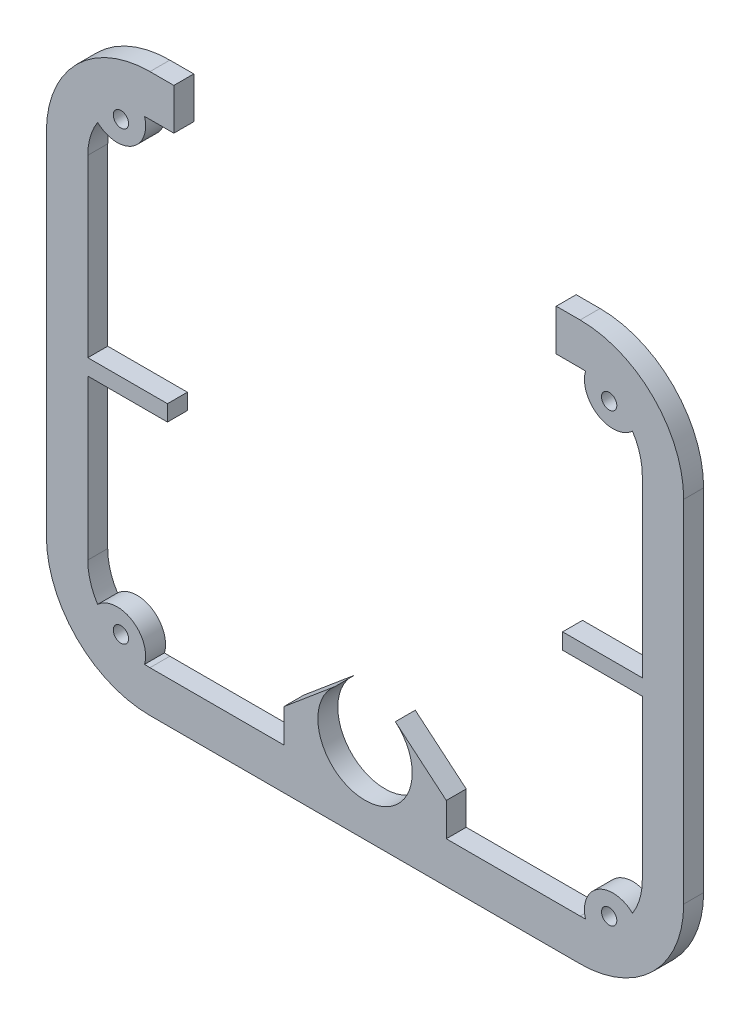
SolidWorks part; units mm, degrees
material "Delrin"
ref_plane "Front Plane" through (0, 0, 0) normal (0, 0, 1) x (1, 0, 0)
ref_plane "Top Plane" through (0, 0, 0) normal (0, 1, 0) x (1, 0, 0)
ref_plane "Right Plane" through (0, 0, 0) normal (1, 0, 0) x (0, 0, -1)
sketch "Sketch1" plane through (0, 0, 0) normal (0, 0, 1) x (1, 0, 0)
  line L0 (-17.145, -18.923) -> (-9.6321, -18.923)
  line L1 (17.145, 22.225) -> (-17.145, 22.225)
  line L2 (25.4, 13.97) -> (25.4, -13.97)
  line L3 (17.145, -22.225) -> (-17.145, -22.225)
  line L4 (-25.4, 13.97) -> (-25.4, -13.97)
  line L5 (25.4, 22.225) -> (-25.4, -22.225) construction
  line L6 (25.4, -22.225) -> (-25.4, 22.225) construction
  line L7 (9.6321, -18.923) -> (17.145, -18.923)
  line L8 (15.748, 0) -> (15.748, -1.27)
  line L9 (-22.098, 0) -> (-15.748, 0)
  line L10 (-22.098, 13.97) -> (-22.098, -13.97)
  line L11 (-1000, 0) -> (49000, 0) construction
  line L12 (-22.098, 0) -> (-22.098, -1.27)
  line L13 (22.098, 13.97) -> (22.098, -13.97)
  line L14 (17.145, 18.923) -> (-17.145, 18.923)
  line L15 (-22.098, -1.27) -> (-15.748, -1.27)
  line L16 (-15.748, 0) -> (-15.748, -1.27)
  line L17 (22.098, 0) -> (15.748, 0)
  line L18 (0, 18.923) -> (0, -18.415) construction
  line L19 (22.098, -1.27) -> (15.748, -1.27)
  line L21 (2.4164, -12.8683) -> (9.6321, -18.923)
  line L22 (-2.4164, -12.8683) -> (-9.6321, -18.923)
  line L36 (17.145, -18.923) -> (-17.145, -18.923) construction
  arc A0 (-2.4164, -12.8683) -> (2.4164, -12.8683) centre (0, -15.748) ccw
  arc A1 (-17.145, 22.225) -> (-25.4, 13.97) centre (-17.145, 13.97) ccw
  arc A2 (17.145, 22.225) -> (25.4, 13.97) centre (17.145, 13.97) cw
  arc A3 (25.4, -13.97) -> (17.145, -22.225) centre (17.145, -13.97) cw
  arc A4 (-17.145, -22.225) -> (-25.4, -13.97) centre (-17.145, -13.97) cw
  arc A5 (-21.3168, 16.6398) -> (-17.5714, 18.9046) centre (-19.7605, 18.2953) ccw
  arc A6 (21.3168, 16.6398) -> (17.5714, 18.9046) centre (19.7605, 18.2953) cw
  arc A7 (17.145, 18.923) -> (22.098, 13.97) centre (17.145, 13.97) cw
  arc A8 (-17.145, 18.923) -> (-22.098, 13.97) centre (-17.145, 13.97) ccw
  circle A9 centre (-19.4575, 17.78) radius 0.6096
  circle A10 centre (19.4575, 17.78) radius 0.6096
  circle A11 centre (-19.4575, -17.78) radius 0.6096
  circle A12 centre (19.4575, -17.78) radius 0.6096
  arc A13 (-17.145, -18.923) -> (-22.098, -13.97) centre (-17.145, -13.97) cw construction
  arc A14 (22.098, -13.97) -> (17.145, -18.923) centre (17.145, -13.97) cw construction
  arc A15 (-22.098, -13.97) -> (-17.145, -18.923) centre (-17.145, -13.97) ccw
  arc A16 (17.145, -18.923) -> (22.098, -13.97) centre (17.145, -13.97) ccw
  arc A17 (21.3168, -16.6398) -> (17.5714, -18.9046) centre (19.7605, -18.2953) ccw
  arc A18 (-21.3168, -16.6398) -> (-17.5714, -18.9046) centre (-19.7605, -18.2953) cw
  point P0 (0, 0)
  dimension "D4" = 7.5184
  dimension "D6" = 8.255
  dimension "D7" = 8.255
  dimension "D8" = 8.255
  dimension "D9" = 8.255
  dimension "D5" = 1.2192
  dimension "D1" = 50.8
  dimension "D2" = 44.45
  dimension "D10" = 3.302
  dimension "D3" = 3.175
  dimension "D11" = 17.78
  dimension "D12" = 19.4575
  dimension "D13" = 15.748
  dimension "D14" = 1.27
  dimension "D15" = 6.35
extrude "Boss-Extrude1" add sketch "Sketch1" along normal blind 1.5875 contours A4 L3 A3 L2 A2 L1 A1 L4 A16 L7 L21 A0 L22 L0 A15 A11 L10 A8 A9 L14 A7 A10 L13 A12 | A9 A8 A5 | A16 A17 A12 | A18 A15 A11 | A7 A10 A6 | L16 L9 L10 L15 | L19 L13 L17 L8 region at (-18.4919, -18.6865, 0) region at (-18.923, -0.635, 0) region at (18.6095, -16.3919, 0) region at (-20.7018, 17.3477, 0) region at (18.923, -0.635, 0) region at (18.4919, 18.6865, 0) region at (22.5049, 19.3299, 0)
sketch "Sketch2" plane through (0, 0, 1.5875) normal (0, 0, 1) x (1, 0, 0)
  line L1 (-9.6321, -18.923) -> (-6.477, -18.923)
  line L2 (-9.6321, -18.923) -> (-9.6321, -16.2756)
  line L3 (-9.6321, -16.2756) -> (-6.477, -16.2756)
  line L4 (-6.477, -18.923) -> (-6.477, -16.2756)
  line L5 (0, -1000) -> (0, 49000) construction
  line L6 (9.6321, -18.923) -> (9.6321, -16.2756)
  line L7 (9.6321, -16.2756) -> (6.477, -16.2756)
  line L8 (6.477, -18.923) -> (6.477, -16.2756)
  line L9 (9.6321, -18.923) -> (6.477, -18.923)
  line L11 (-15.24, 18.923) -> (15.24, 18.923)
  line L12 (-15.24, 18.923) -> (-15.24, 22.225)
  line L13 (-15.24, 22.225) -> (15.24, 22.225)
  line L14 (15.24, 18.923) -> (15.24, 22.225)
  line L16 (17.145, 18.923) -> (-17.145, 18.923) construction
  line L17 (-2.4164, -12.8683) -> (-9.6321, -18.923) construction
  line L18 (17.145, 22.225) -> (-17.145, 22.225) construction
  point P25 (0, 22.225)
  dimension "D1" = 6.477
  dimension "D2" = 30.48
extrude "Cut-Extrude1" cut sketch "Sketch2" against normal up to next
